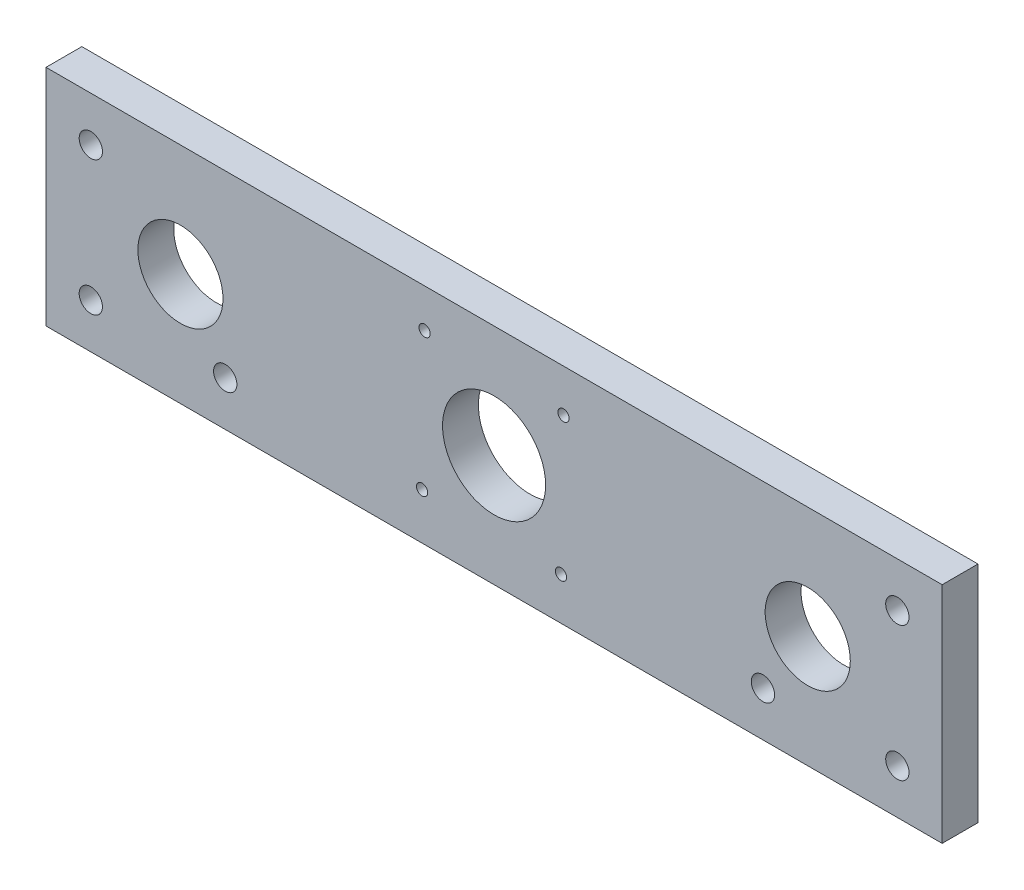
SolidWorks part; units mm, degrees
ref_plane "Ön Düzlem" through (0, 0, 0) normal (0, 0, 1) x (1, 0, 0)
ref_plane "Üst Düzlem" through (0, 0, 0) normal (0, 1, 0) x (1, 0, 0)
ref_plane "Sağ Düzlem" through (0, 0, 0) normal (1, 0, 0) x (0, 0, -1)
sketch "Çizim1" plane through (0, 0, 0) normal (0, 0, 1) x (1, 0, 0)
  line L0 (41.8502, -1.6887) -> (41.8502, -51.6887) construction
  line L1 (-58.1498, -1.6887) -> (141.8502, -1.6887)
  line L2 (-58.1498, -1.6887) -> (-58.1498, -51.6887)
  line L3 (-58.1498, -51.6887) -> (141.8502, -51.6887)
  line L4 (141.8502, -1.6887) -> (141.8502, -51.6887)
  circle A0 centre (-28.1498, -26.6887) radius 4
  circle A1 centre (-28.1498, -26.6887) radius 9.5
  circle A2 centre (111.8502, -26.6887) radius 4
  circle A3 centre (111.8502, -26.6887) radius 9.5
  circle A4 centre (-48.1498, -11.6887) radius 2.283
  circle A5 centre (-48.1498, -41.6887) radius 2.4763
  circle A6 centre (131.8502, -41.6887) radius 2.4763
  circle A7 centre (131.8502, -11.6887) radius 2.283
  dimension "D3" = 8
  dimension "D4" = 30
  dimension "D5" = 19
  dimension "D6" = 19
  dimension "D7" = 30
  dimension "D8" = 25
  dimension "D9" = 10
  dimension "D10" = 10
  dimension "D11" = 10
  dimension "D12" = 10
  dimension "D1" = 200
  dimension "D2" = 50
  dimension "25" = 25
extrude "Yükseklik-Ekstrüzyon1" add sketch "Çizim1" along normal blind 8 contours L1 L0 L3 L4 A7 A3 A6 | L0 L1 L2 L3 A5 A4 A1 | A4 | A5 | A7 | A6 region at (90.3342, -26.6794, 0) region at (-6.6338, -26.6794, 0) region at (-48.1498, -11.6887, 0) region at (-48.1498, -41.6887, 0) region at (131.8502, -41.6887, 0) region at (131.8502, -11.6887, 0)
hole_wizard "M5 Helisarmal için Zıvana matkabı1" positions "Çizim2" profile "Çizim3" hole size "M5x0.8" standard "ANSI Metric" end condition up to next
sketch "Çizim2" plane through (0, 0, 8) normal (0, 0, 1) x (1, 0, 0)
  point P0 (-48.1498, -11.6887)
  point P3 (-48.1498, -41.6887)
  point P6 (131.8502, -41.6887)
  point P9 (131.8502, -11.6887)
sketch "Çizim3" plane through (-48.1498, -11.6887, 8) normal (1, 0, 0) x (0, -1, 0)
  line L0 (0, 0) -> (0, 8)
  line L1 (0, 8) -> (2.6, 8)
  line L2 (2.6, 8) -> (2.6, 0)
  line L5 (2.6, 0) -> (0, 0)
  line L11 (0, -6.35) -> (0, 107.95) construction
  dimension "Thru Hole Dia." = 5.2
  dimension "Thru Hole Depth" = 8
sketch "Çizim4" plane through (0, 0, 0) normal (0, 0, -1) x (-1, 0, 0)
  circle A0 centre (-41.8502, -26.6887) radius 11.5
  circle A1 centre (-57.3502, -11.1887) radius 1.25
  circle A2 centre (-56.7815, -42.1887) radius 1.25
  circle A3 centre (-25.7815, -41.329) radius 1.25
  circle A4 centre (-26.3502, -10.329) radius 1.25
  dimension "D1" = 23
extrude "Kes-Ekstrüzyon1" cut sketch "Çizim4" against normal blind 10 and the other way blind 10
sketch "Çizim5" plane through (0, 0, 8) normal (0, 0, 1) x (1, 0, 0)
  line L0 (-58.1498, -51.6887) -> (141.8502, -51.6887) construction
  line L1 (-58.1498, -1.6887) -> (-58.1498, -51.6887) construction
  line L2 (41.8502, -1.6887) -> (41.8502, -9.312) construction
  line L3 (-58.1498, -1.6887) -> (141.8502, -1.6887) construction
  circle A0 centre (-18.1498, -41.6887) radius 3.103
  circle A1 centre (101.8502, -41.6887) radius 3.103
  dimension "D1" = 10
  dimension "D2" = 40
hole_wizard "M5 Helisarmal için Zıvana matkabı2" positions "3B Çizim1" profile "Çizim6" hole size "M5x0.8" standard "ANSI Metric" end condition up to next
sketch3d "3B Çizim1"
  point P0 (-18.1498, -41.6887, 8)
  point P3 (101.8502, -41.6887, 8)
sketch "Çizim6" plane through (-18.1498, -41.6887, 8) normal (1, 0, 0) x (0, -1, 0)
  line L0 (0, 0) -> (0, 8)
  line L1 (0, 8) -> (2.6, 8)
  line L2 (2.6, 8) -> (2.6, 0)
  line L5 (2.6, 0) -> (0, 0)
  line L11 (0, -6.35) -> (0, 107.95) construction
  dimension "Thru Hole Dia." = 5.2
  dimension "Thru Hole Depth" = 8
